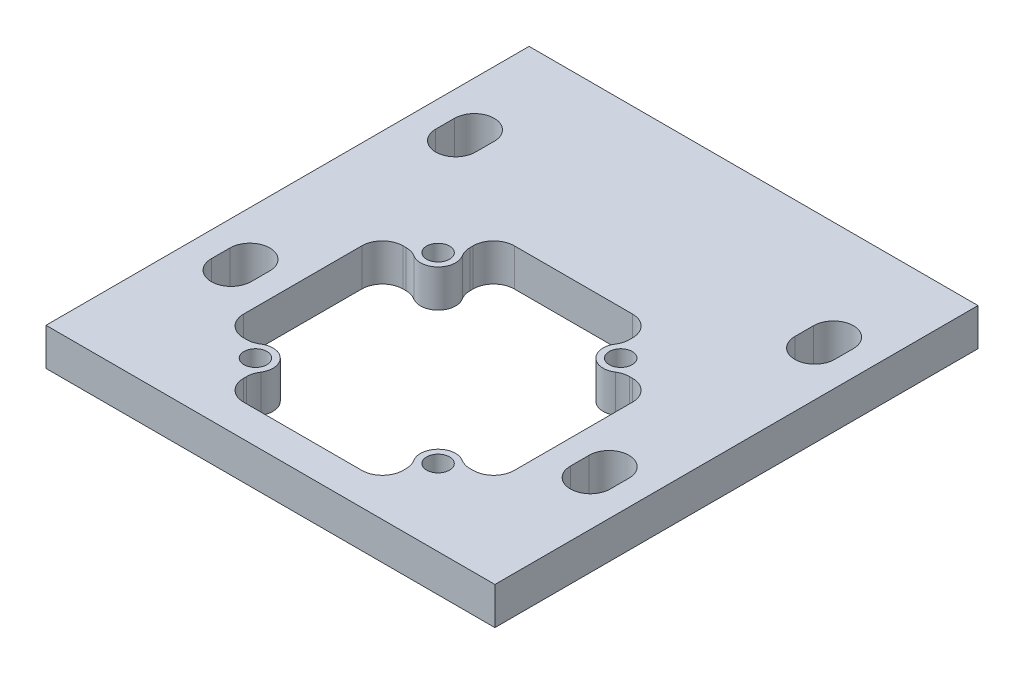
SolidWorks part; units mm, degrees
note: '?' marks a value the reader was unsure of.
ref_plane "Front Plane" through (0, 0, 0) normal (0, 0, 1) x (1, 0, 0)
ref_plane "Top Plane" through (0, 0, 0) normal (0, 1, 0) x (1, 0, 0)
ref_plane "Right Plane" through (0, 0, 0) normal (1, 0, 0) x (0, 0, -1)
sketch "Sketch1" plane through (0, 0, 0) normal (0, 1, 0) x (1, 0, 0)
  line L1 (-38.1, 41) -> (38.1, 41)
  line L2 (-38.1, 41) -> (-38.1, -41)
  line L3 (-38.1, -41) -> (38.1, -41)
  line L4 (38.1, 41) -> (38.1, -41)
  line L5 (-38.1, 41) -> (38.1, -41) construction
  line L6 (-38.1, -41) -> (38.1, 41) construction
  point P0 (0, 0)
  dimension "D1" = 76.2
  dimension "D2" = 82
extrude "Boss-Extrude1" add sketch "Sketch1" along normal mid plane 6.35
sketch "Sketch16" plane through (0, 3.175, 0) normal (0, 1, 0) x (1, 0, 0)
  line L0 (38.1, 41) -> (-38.1, 41) construction
  line L1 (-38.1, 41) -> (-38.1, -41) construction
  line L2 (0, -55) -> (0, 55) construction
  point P0 (-17.3, 5.451)
  point P10 (17.3, 5.451)
  dimension "D1" = 35.549
  dimension "D2" = 20.8
sketch "Sketch2" plane through (0, 3.175, 0) normal (0, 1, 0) x (1, 0, 0)
  line L1 (-14.8273, 27.305) -> (14.8272, 27.305)
  line L2 (-14.8273, 27.305) -> (-14.8272, -27.305)
  line L3 (-14.8272, -27.305) -> (14.8273, -27.305)
  line L4 (14.8272, 27.305) -> (14.8273, -27.305)
  line L5 (-14.8273, 27.305) -> (14.8273, -27.305) construction
  line L6 (-14.8272, -27.305) -> (14.8272, 27.305) construction
  point P0 (0, 0)
  dimension "D1" = 29.6545
  dimension "D2" = 54.61
extrude "Cut-Extrude1" [suppressed] cut sketch "Sketch2" against normal through all
hole_wizard "M2.5 Clearance Hole1" [suppressed] positions "Sketch3" profile "Sketch4" hole size "M2.5" standard "ANSI Metric"
sketch "Sketch3" plane through (0, 3.175, 0) normal (0, 1, 0) x (1, 0, 0)
  point P0 (-17.3, 24.551)
  point P3 (-11, 29.851)
  point P6 (-17.3, 2.551)
  point P9 (-17.3, -19.449)
sketch "Sketch4" plane through (-17.3, 3.175, -24.551) normal (1, 0, 0) x (0, 0, 1)
  line L0 (0, 0) -> (0, 6.35)
  line L1 (0, 6.35) -> (1.45, 6.35)
  line L2 (1.45, 6.35) -> (1.45, 0)
  line L5 (1.45, 0) -> (0, 0)
  line L11 (0, -6.35) -> (0, 107.95) construction
  dimension "Thru Hole Dia." = 2.9
  dimension "Thru Hole Depth" = 6.35
sketch "Sketch8" plane through (0, 3.175, 0) normal (0, 1, 0) x (1, 0, 0)
  line L0 (-30.48, -17.1875) -> (-30.48, -14.0125) construction
  line L1 (-33.8582, -17.1875) -> (-33.8582, -14.0125)
  line L2 (-27.1018, -17.1875) -> (-27.1018, -14.0125)
  line L3 (-30.48, 20.9125) -> (-30.48, 24.0875) construction
  line L4 (-33.8582, 20.9125) -> (-33.8582, 24.0875)
  line L5 (-27.1018, 20.9125) -> (-27.1018, 24.0875)
  line L6 (-38.1, -41) -> (38.1, -41) construction
  line L7 (-38.1, 41) -> (-38.1, -41) construction
  arc A0 (-33.8582, -17.1875) -> (-27.1018, -17.1875) centre (-30.48, -17.1875) ccw
  arc A1 (-27.1018, -14.0125) -> (-33.8582, -14.0125) centre (-30.48, -14.0125) ccw
  arc A2 (-33.8582, 20.9125) -> (-27.1018, 20.9125) centre (-30.48, 20.9125) ccw
  arc A3 (-27.1018, 24.0875) -> (-33.8582, 24.0875) centre (-30.48, 24.0875) ccw
  point P2 (-30.48, -15.6)
  point P7 (-30.48, 22.5)
  dimension "D5" = 3.3782
  dimension "D1" = 38.1
  dimension "D2" = 25.4
  dimension "D3" = 7.62
  dimension "D4" = 3.175
extrude "Cut-Extrude2" cut sketch "Sketch8" against normal through all
mirror "Mirror1" about plane through (0, 0, 0) normal (1, 0, 0) of "Cut-Extrude2", "M2.5 Clearance Hole1"
sketch "Sketch9" [suppressed] plane through (0, 3.175, 0) normal (0, 1, 0) x (1, 0, 0)
  line L0 (-14.8272, -27.305) -> (14.8273, -27.305) construction
  line L1 (-38.1, -27.305) -> (38.1, -27.305)
  line L2 (-38.1, -27.305) -> (-38.1, -38.1)
  line L3 (-38.1, -38.1) -> (38.1, -38.1)
  line L4 (38.1, -27.305) -> (38.1, -38.1)
  line L5 (-38.1, -27.305) -> (38.1, -38.1) construction
  line L6 (-38.1, -38.1) -> (38.1, -27.305) construction
  line L8 (38.1, 37.69) -> (-38.1, 37.69)
  line L9 (38.1, 37.69) -> (38.1, 38.1)
  line L10 (38.1, 38.1) -> (-38.1, 38.1)
  line L11 (-38.1, 37.69) -> (-38.1, 38.1)
  line L12 (38.1, 37.69) -> (-38.1, 38.1) construction
  line L13 (38.1, 38.1) -> (-38.1, 37.69) construction
  point P0 (0, -32.7025)
  point P6 (0, 37.895)
  dimension "D1" = 0.41
extrude "Cut-Extrude3" [suppressed] cut sketch "Sketch9" against normal through all
sketch "Sketch13" [suppressed] plane through (0, -3.175, 0) normal (0, -1, 0) x (1, 0, 0)
  line L0 (-38.1, -31.213) -> (-22.352, -37.69)
  line L1 (-38.1, -38.1) -> (-38.1, 38.1) construction
  line L2 (-38.1, -37.69) -> (38.1, -37.69) construction
  line L3 (-22.352, -37.69) -> (-38.1, -37.69)
  line L4 (-38.1, -37.69) -> (-38.1, -31.213)
  dimension "D1" = 6.477
  dimension "D2" = 15.748
extrude "Cut-Extrude4" [suppressed] cut sketch "Sketch13" against normal through all
sketch "Sketch15" [suppressed] plane through (0, 3.175, 0) normal (0, 1, 0) x (1, 0, 0)
  line L0 (-38.1, 38.1) -> (-38.1, -38.1) construction
  line L2 (-38.1, 37.69) -> (38.1, 37.69) construction
  point P0 (-17.3, 2.551)
  dimension "D1" = 20.8
  dimension "D2" = 35.139
mirror "Mirror3" [suppressed] about plane through (0, 0, 0) normal (1, 0, 0)
fillet "Fillet1" [suppressed] radius 3.175
mirror "Mirror2" [suppressed] about plane through (0, 0, 0) normal (1, 0, 0)
sketch "Sketch10" [suppressed] plane through (0, 0, -38.1) normal (0, 0, -1) x (-1, 0, 0)
  line L4 (-25.4, -3.175) -> (25.4, -3.175)
  line L5 (25.4, -3.175) -> (25.4, 3.175)
  line L6 (25.4, 3.175) -> (-25.4, 3.175)
  line L7 (-25.4, 3.175) -> (-25.4, -3.175)
  line L8 (-25.4, -3.175) -> (25.4, -3.175)
  line L9 (25.4, -3.175) -> (25.4, 3.175)
  line L10 (25.4, 3.175) -> (-25.4, 3.175)
  line L11 (-25.4, 3.175) -> (-25.4, -3.175)
  dimension "D1" = 0
extrude "Boss-Extrude2" [suppressed] add sketch "Sketch10" along normal mid plane 12.7
hole_wizard "#10 Clearance Hole1" [suppressed] positions "Sketch11" profile "Sketch12" hole size "#10" standard "ANSI Inch"
sketch "Sketch11" plane through (0, 3.175, 0) normal (0, 1, 0) x (1, 0, 0)
  line L0 (-19.05, 38.1) -> (19.05, 38.1)
  line L3 (-25.4, 44.45) -> (25.4, 44.45) construction
  point P0 (-19.05, 38.1)
  point P2 (19.05, 38.1)
  point P9 (0, 38.1)
  dimension "D1" = 6.35
  dimension "D2" = 38.1
sketch "Sketch12" plane through (-19.05, 3.175, -38.1) normal (1, 0, 0) x (0, 0, 1)
  line L0 (0, 0) -> (0, 14.2338)
  line L1 (0, 14.2338) -> (2.5527, 12.7)
  line L2 (2.5527, 12.7) -> (2.5527, 0)
  line L5 (2.5527, 0) -> (0, 0)
  line L10 (0, 14.2338) -> (-2.5527, 12.7) construction
  line L11 (0, -6.35) -> (0, 107.95) construction
  dimension "Hole Dia." = 5.1054
  dimension "Hole Depth" = 12.7
  dimension "Drill Angle" = 118
sketch "Sketch17" plane through (0, 3.175, 0) normal (0, 1, 0) x (1, 0, 0)
  line L0 (-17.3, 5.451) -> (17.3, 5.451) construction
  line L1 (-21, -33.549) -> (21, -33.549) construction
  line L2 (-21, -33.549) -> (-21, 8.451) construction
  line L3 (-21, 8.451) -> (21, 8.451) construction
  line L4 (21, -33.549) -> (21, 8.451) construction
  line L5 (-21, -33.549) -> (21, 8.451) construction
  line L6 (-21, 8.451) -> (21, -33.549) construction
  line L7 (-15.5, -28.049) -> (15.5, -28.049) construction
  line L8 (-15.5, -28.049) -> (-15.5, 2.951) construction
  line L9 (-15.5, 2.951) -> (15.5, 2.951) construction
  line L10 (15.5, -28.049) -> (15.5, 2.951) construction
  line L11 (-15.5, -28.049) -> (15.5, 2.951) construction
  line L12 (-15.5, 2.951) -> (15.5, -28.049) construction
  point P0 (0, -12.549)
  point P5 (0, -12.549)
  point P10 (0, 5.451)
  dimension "D1" = 31
  dimension "D2" = 42
  dimension "D3" = 18
hole_wizard "M3.5 Clearance Hole1" positions "Sketch19" profile "Sketch20" hole size "M3.5" standard "ANSI Metric" end condition through all
sketch "Sketch19" plane through (0, 3.175, 0) normal (0, 1, 0) x (1, 0, 0)
  point P0 (-15.5, 2.951)
  point P3 (15.5, 2.951)
  point P6 (15.5, -28.049)
  point P9 (-15.5, -28.049)
sketch "Sketch20" plane through (-15.5, 3.175, -2.951) normal (1, 0, 0) x (0, 0, 1)
  line L0 (0, 0) -> (0, 6.35)
  line L1 (0, 6.35) -> (1.95, 6.35)
  line L2 (1.95, 6.35) -> (1.95, 0)
  line L5 (1.95, 0) -> (0, 0)
  line L11 (0, -6.35) -> (0, 107.95) construction
  dimension "Thru Hole Dia." = 3.9
  dimension "Thru Hole Depth" = 6.35
sketch "Sketch21" plane through (0, 3.175, 0) normal (0, 1, 0) x (1, 0, 0)
  line L0 (-12.9661, 8.451) -> (-12.9661, 4.557) construction
  line L1 (-12.9661, 8.451) -> (12.9661, 8.451) construction
  line L2 (-21, 2.6996) -> (-21, -27.7976) construction
  line L3 (-12.9661, -33.549) -> (12.9661, -33.549) construction
  line L4 (21, 2.6996) -> (21, -27.7976) construction
  line L5 (-15.5, 2.951) -> (15.5, -28.049) construction
  line L7 (12.9661, 8.451) -> (12.9661, 4.557) construction
  line L9 (-21, -27.7976) -> (-18.4894, -27.7976) construction
  line L11 (12.9661, -33.549) -> (12.9661, -29.655) construction
  line L13 (-21, -33.549) -> (-21, 8.451) construction
  line L16 (-21, -33.549) -> (21, -33.549) construction
  line L18 (-21, 8.451) -> (21, 8.451) construction
  line L19 (21, -33.549) -> (21, 8.451) construction
  line L22 (-18.4894, 2.6996) -> (-21, 2.6996) construction
  line L23 (-33.8582, 24.0875) -> (-33.8582, 20.9125) construction
  line L24 (18.4894, 2.6996) -> (21, 2.6996) construction
  line L25 (18.4894, -27.7976) -> (21, -27.7976) construction
  line L26 (-12.9661, -29.655) -> (-12.9661, -33.549) construction
  arc A0 (-18.4894, 2.6996) -> (-12.9661, 4.557) centre (-15.5, 2.951) ccw construction
  arc A1 (12.9661, 4.557) -> (18.4894, 2.6996) centre (15.5, 2.951) ccw construction
  arc A2 (18.4894, -27.7976) -> (12.9661, -29.655) centre (15.5, -28.049) ccw construction
  arc A3 (-12.9661, -29.655) -> (-18.4894, -27.7976) centre (-15.5, -28.049) ccw construction
  arc A9 (-12.9661, 0.0481) -> (-12.7032, -0.1214) centre (-11.254, 2.4162) ccw construction
  point P4 (0, -12.549)
  point P13 (0, -12.549)
  dimension "D2" = 6
sketch "Sketch23" plane through (0, 3.175, 0) normal (0, 1, 0) x (1, 0, 0)
  line L0 (-12.9861, 8.471) -> (-12.9861, 4.5512)
  line L1 (-12.9861, 8.471) -> (12.9861, 8.471)
  line L2 (-21.02, 0.4371) -> (-21.02, -25.5351)
  line L3 (-12.9861, -33.569) -> (12.9861, -33.569)
  line L4 (21.02, 0.4371) -> (21.02, -25.5351)
  line L5 (12.9861, 8.471) -> (12.9861, 4.5512)
  line L6 (-21.02, -25.5351) -> (-17.1002, -25.5351)
  line L7 (12.9861, -33.569) -> (12.9861, -29.6492)
  line L8 (-17.1002, 0.4371) -> (-21.02, 0.4371)
  line L9 (17.1002, 0.4371) -> (21.02, 0.4371)
  line L10 (17.1002, -25.5351) -> (21.02, -25.5351)
  line L11 (-12.9861, -29.6492) -> (-12.9861, -33.569)
  line L16 (21, 2.6996) -> (21, -27.7976) construction
  line L19 (-12.9661, 8.451) -> (12.9661, 8.451) construction
  line L20 (12.9661, 8.451) -> (12.9661, 4.557) construction
  arc A0 (-17.1002, 0.4371) -> (-12.9861, 4.5512) centre (-15.5, 2.951) ccw
  arc A1 (12.9861, 4.5512) -> (17.1002, 0.4371) centre (15.5, 2.951) ccw
  arc A2 (17.1002, -25.5351) -> (12.9861, -29.6492) centre (15.5, -28.049) ccw
  arc A3 (-12.9861, -29.6492) -> (-17.1002, -25.5351) centre (-15.5, -28.049) ccw
  arc A4 (12.9661, 4.557) -> (18.4894, 2.6996) centre (15.5, 2.951) ccw construction
  circle A5 centre (-15.5, 2.951) radius 1.95 construction
  dimension "D2" = 0.02
  dimension "D1" = 0.02
  dimension "D4" = 0.02
  dimension "D5" = 0.02
extrude "Cut-Extrude6" cut sketch "Sketch23" against normal through all
sketch "Sketch24" plane through (0, 3.175, 0) normal (0, 1, 0) x (1, 0, 0)
  line L0 (-18.9796, 0.9845) -> (-19.4796, 0.9845)
  line L1 (-22.9796, -2.5155) -> (-22.9796, -22.5825)
  line L2 (-19.4796, -26.0825) -> (-18.9796, -26.0825)
  line L4 (-15.5, 2.951) -> (15.5, -28.049) construction
  line L5 (-12.9861, 4.5512) -> (-7.9861, 4.5512)
  line L6 (-7.9861, 4.5512) -> (-7.9861, -29.6492)
  line L7 (-7.9861, -29.6492) -> (-12.9861, -29.6492)
  arc A0 (-17.1002, 0.4371) -> (-18.9796, 0.9845) centre (-18.9796, -2.5155) ccw
  arc A1 (-17.1002, 0.4371) -> (-12.9861, 4.5512) centre (-15.5, 2.951) ccw construction
  arc A3 (-19.4796, 0.9845) -> (-22.9796, -2.5155) centre (-19.4796, -2.5155) ccw
  arc A7 (-18.9796, -26.0825) -> (-17.1002, -25.5351) centre (-18.9796, -22.5825) ccw
  arc A8 (-22.9796, -22.5825) -> (-19.4796, -26.0825) centre (-19.4796, -22.5825) ccw
  arc A9 (-17.1002, 0.4371) -> (-12.9861, 4.5512) centre (-15.5, 2.951) ccw
  arc A10 (-12.9861, -29.6492) -> (-17.1002, -25.5351) centre (-15.5, -28.049) ccw construction
  arc A11 (-12.9861, -29.6492) -> (-17.1002, -25.5351) centre (-15.5, -28.049) ccw
  point P9 (0, -12.549)
  dimension "D3" = 5
  dimension "D4" = 3.5
  dimension "D5" = 0.5
extrude "Cut-Extrude7" cut sketch "Sketch24" against normal through all
ref_axis "Axis1" through (0, 3.175, 12.549) along (0, 1, 0)?
pattern_circular "CirPattern1" count 4 over 360 about axis through (0, 0, 12.549) along (0, 1, 0) of "Cut-Extrude7"
